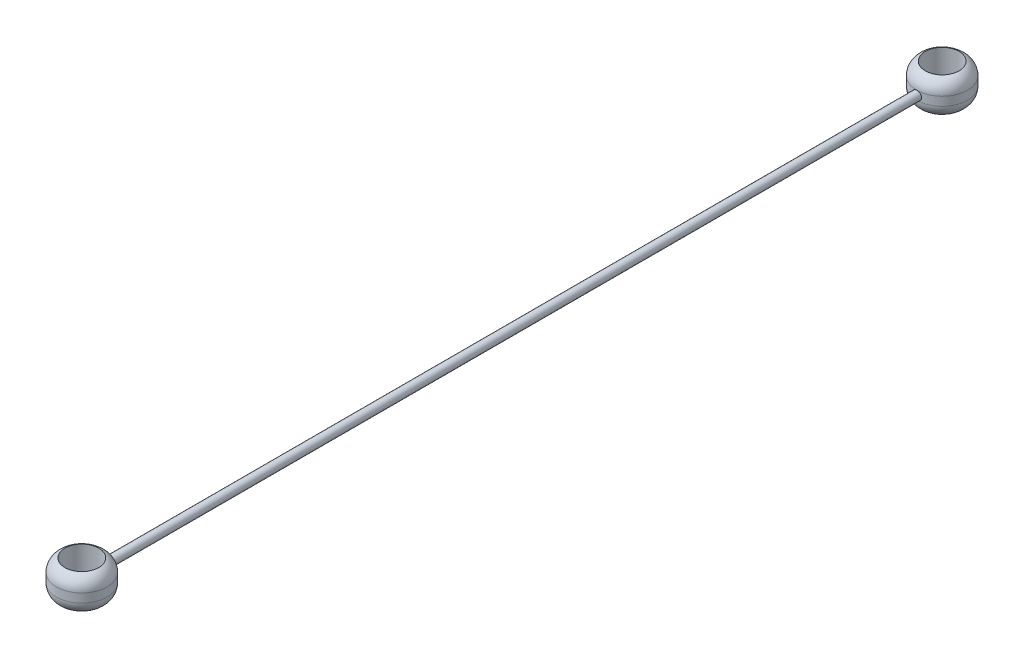
SolidWorks part; units mm, degrees
ref_plane "前视基准面" through (0, 0, 0) normal (0, 0, 1) x (1, 0, 0)
ref_plane "上视基准面" through (0, 0, 0) normal (0, 1, 0) x (1, 0, 0)
ref_plane "右视基准面" through (0, 0, 0) normal (1, 0, 0) x (0, 0, -1)
sketch "草图1" plane through (0, 0, 0) normal (0, 1, 0) x (1, 0, 0)
  circle A0 centre (0, 55.3251) radius 5
  circle A1 centre (0, 55.3251) radius 7.5
extrude "凸台-拉伸1" add sketch "草图1" along normal blind 10
fillet "圆角1" radius 4 2 edges at (0, 0, -47.8251) (0, 10, -47.8251)
ref_plane "基准面5" through (0, 0, -48) normal (0, 0, 1) x (1, 0, 0)
sketch "草图4" plane through (0, 0, -48) normal (0, 0, 1) x (1, 0, 0)
  circle A0 centre (0, 4.9873) radius 1.3
  point P2 (0, 4.9873)
extrude "凸台-拉伸3" add sketch "草图4" along normal blind 120
ref_plane "基准面6" through (0, 0, 72) normal (0, 0, 1) x (1, 0, 0)
mirror "镜向6" about plane through (0, 0, 72) normal (0, 0, 1) of "凸台-拉伸1", "凸台-拉伸3"
mirror "镜向7" about plane through (0, 0, 72) normal (0, 0, 1) of "凸台-拉伸1", "圆角1"
